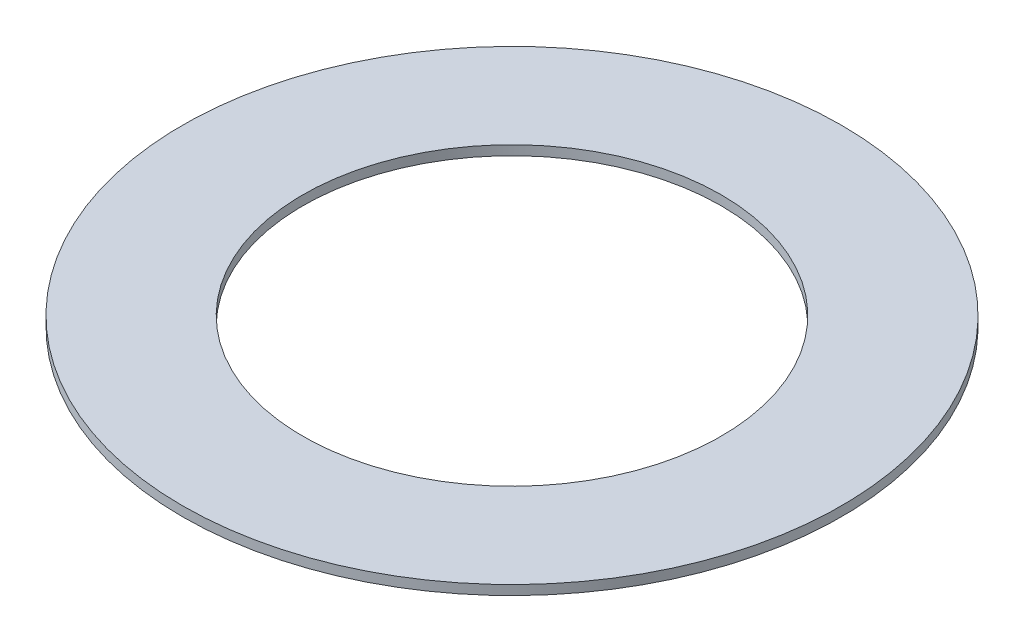
SolidWorks part; units mm, degrees
material "Hexcel AS4C (3000 Filaments)"
ref_plane "Front Plane" through (0, 0, 0) normal (0, 0, 1) x (1, 0, 0)
ref_plane "Top Plane" through (0, 0, 0) normal (0, 1, 0) x (1, 0, 0)
ref_plane "Right Plane" through (0, 0, 0) normal (1, 0, 0) x (0, 0, -1)
sketch "Sketch1" plane through (0, 0, 0) normal (0, 0, 1) x (1, 0, 0)
  line L0 (-69.5, 12.91) -> (-69.5, 9.735) construction
  line L1 (-69.5, 12.91) -> (-109.5, 12.91) construction
  line L2 (-109.5, 9.735) -> (-69.5, 9.735) construction
  line L3 (-109.5, 12.91) -> (-109.5, 9.735) construction
  line L4 (-69.5, 12.91) -> (-69.5, 9.735)
  line L5 (-69.5, 12.91) -> (-109.5, 12.91)
  line L6 (-109.5, 9.735) -> (-69.5, 9.735)
  line L7 (-109.5, 12.91) -> (-109.5, 9.735)
  line L8 (0, -200069.0475) -> (0, 200086.9028) construction
  line L9 (0, -200069.0475) -> (0, 200086.9028) construction
revolve "Revolve1" add sketch "Sketch1" angle 360 about L9
